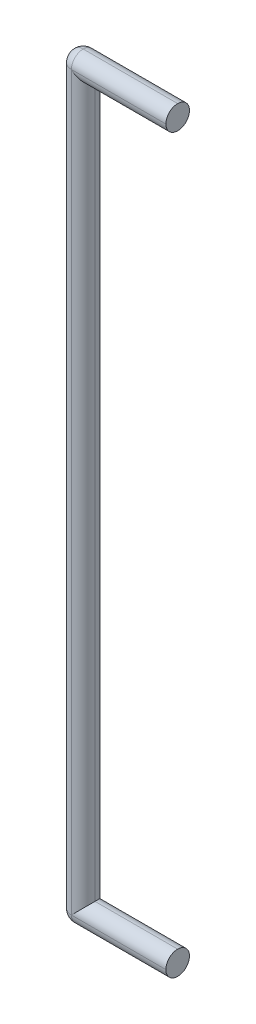
SolidWorks part; units mm, degrees
ref_plane "Front" through (0, 0, 0) normal (0, 0, 1) x (1, 0, 0)
ref_plane "Top" through (0, 0, 0) normal (0, 1, 0) x (1, 0, 0)
ref_plane "Right" through (0, 0, 0) normal (1, 0, 0) x (0, 0, -1)
sketch "草图1" plane through (0, 0, 0) normal (0, 1, 0) x (1, 0, 0)
  line L1 (0.5, -0.5) -> (-0.5, -0.5)
  line L2 (0.5, -0.5) -> (0.5, 0.5)
  line L3 (0.5, 0.5) -> (-0.5, 0.5)
  line L4 (-0.5, -0.5) -> (-0.5, 0.5)
  line L5 (0.5, -0.5) -> (-0.5, 0.5) construction
  line L6 (0.5, 0.5) -> (-0.5, -0.5) construction
  point P0 (0, 0)
  dimension "D1" = 1
  dimension "D2" = 1
extrude "凸台-拉伸1" add sketch "草图1" along normal blind 30
sketch "草图2" plane through (0, 0, 0) normal (1, 0, 0) x (0, 0, -1)
  line L0 (-0.5, 0) -> (0.5, 0) construction
  line L1 (-0.5, -1) -> (0.5, -1)
  line L2 (-0.5, -1) -> (-0.5, 0)
  line L3 (-0.5, 0) -> (0.5, 0)
  line L4 (0.5, -1) -> (0.5, 0)
  line L5 (-0.5, -1) -> (0.5, 0) construction
  line L6 (-0.5, 0) -> (0.5, -1) construction
  line L7 (0, 1.8428) -> (0, -2.8428) construction
  line L8 (-0.5, 30) -> (0.5, 30) construction
  line L9 (0.5, 30) -> (-0.5, 30)
  line L10 (0.5, 30) -> (0.5, 31)
  line L11 (0.5, 31) -> (-0.5, 31)
  line L12 (-0.5, 30) -> (-0.5, 31)
  line L13 (0.5, 30) -> (-0.5, 31) construction
  line L14 (0.5, 31) -> (-0.5, 30) construction
  point P0 (0, -0.5)
  point P10 (0.5, 30.5)
  point P11 (0, 30.5)
  dimension "D1" = 1
  dimension "D2" = 1
  dimension "D3" = 1
  dimension "D4" = 1
extrude "凸台-拉伸2" add sketch "草图2" along normal blind 4 and the other way blind 0.5
fillet "圆角1" radius 0.5 4 edges at (1.75, -1, 0.5) (2.25, 0, 0.5) (2.25, 0, -0.5) (1.75, -1, -0.5)
fillet "圆角2" radius 0.5 6 edges at (-0.5, -0.8536, -0.3536) (-0.5, -0.8536, 0.3536) (-0.5, 15.25, -0.5) (-0.5, 15.25, 0.5) (0.5, 14.75, -0.5) (0.5, 14.75, 0.5)
fillet "圆角3" radius 0.5 6 edges at (2, 31, 0.5) (-0.3536, 31, 0.3536) (-0.3536, 31, -0.3536) (2, 30, 0.5) (2, 30, -0.5) (2, 31, -0.5)
